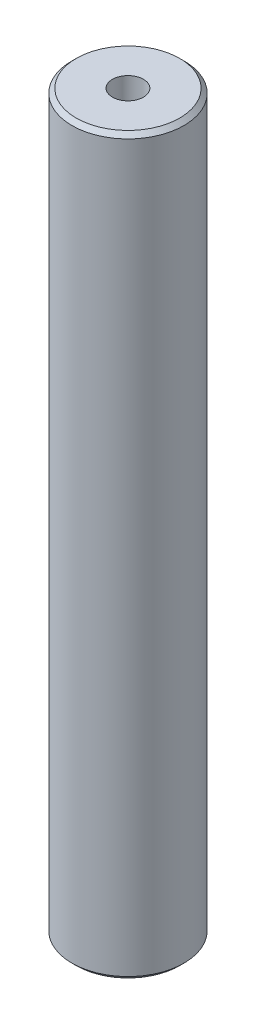
SolidWorks part; units mm, degrees
ref_plane "Front Plane" through (0, 0, 0) normal (0, 0, 1) x (1, 0, 0)
ref_plane "Top Plane" through (0, 0, 0) normal (0, 1, 0) x (1, 0, 0)
ref_plane "Right Plane" through (0, 0, 0) normal (1, 0, 0) x (0, 0, -1)
sketch "Sketch1" plane through (0, 0, 0) normal (0, 1, 0) x (1, 0, 0)
  circle A0 centre (0, 0) radius 15
  dimension "SHAFT_OD" = 30
extrude "Boss-Extrude1" add sketch "Sketch1" along normal blind 196.4798
sketch "Sketch2" plane through (0, 0, 0) normal (0, 1, 0) x (1, 0, 0)
  circle A0 centre (0, 0) radius 4.1503
  dimension "BORE_D" = 8.3007
extrude "Cut-Extrude1" cut sketch "Sketch2" along normal through all
chamfer "Chamfer1" distance 1.1541 angle 45 2 edges at (0, 196.4798, 15) (0, 0, 15)
